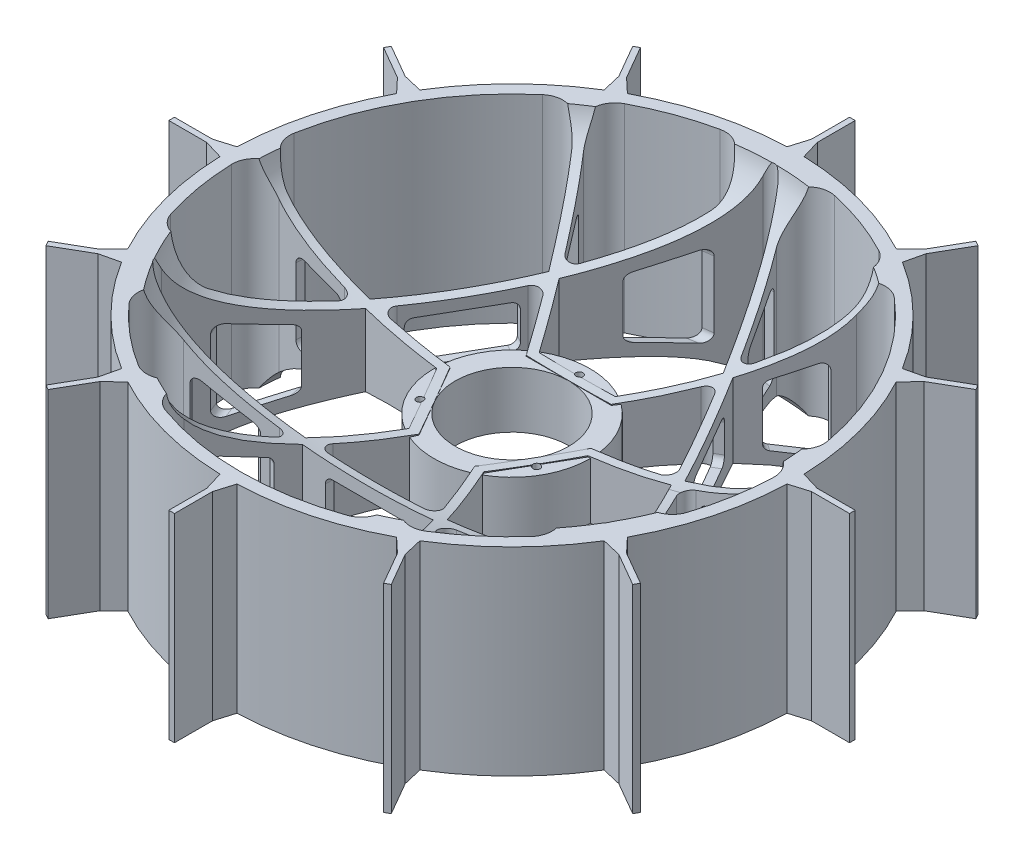
SolidWorks part; units mm, degrees
material "7075-O (SS)"
ref_plane "Front Plane" through (0, 0, 0) normal (0, 0, 1) x (1, 0, 0)
ref_plane "Top Plane" through (0, 0, 0) normal (0, 1, 0) x (1, 0, 0)
ref_plane "Right Plane" through (0, 0, 0) normal (1, 0, 0) x (0, 0, -1)
sketch "Sketch1" plane through (0, 0, 0) normal (0, 1, 0) x (1, 0, 0)
  circle A0 centre (0, 0) radius 100
  circle A1 centre (0, 0) radius 95.625
  dimension "D1" = 200
  dimension "D2" = 191.25
extrude "Boss-Extrude1" add sketch "Sketch1" along normal blind 70
sketch "Sketch5" plane through (0, 10, 0) normal (0, 1, 0) x (1, 0, 0)
  line L2 (-11.875, 8) -> (-11.875, -8)
  line L3 (11.875, -8) -> (11.875, 8)
  line L4 (-11.875, 8) -> (-11.875, -8)
  line L5 (11.875, -8) -> (11.875, 8)
  arc A15 (-4.1565, 8.4932) -> (-11.875, 8) centre (-8, 8) ccw
  arc A16 (-11.875, -8) -> (-8, -11.875) centre (-8, -8) ccw
  arc A17 (-8, -11.875) -> (-4.1565, -8.4932) centre (-8, -8) ccw
  arc A18 (-2.0488, -6.6387) -> (-4.1565, -8.4932) centre (-2.0488, -8.7637) ccw
  arc A19 (-1.5651, -6.6945) -> (-2.0488, -6.6387) centre (-2.0488, -8.7637) ccw
  arc A20 (-1.5651, -6.6945) -> (0, -6.875) centre (0, 0) ccw
  arc A21 (0, -6.875) -> (1.5651, -6.6945) centre (0, 0) ccw
  arc A22 (2.0488, -6.6387) -> (1.5651, -6.6945) centre (2.0488, -8.7637) ccw
  arc A23 (4.1565, -8.4932) -> (2.0488, -6.6387) centre (2.0488, -8.7637) ccw
  arc A24 (4.1565, -8.4932) -> (8, -11.875) centre (8, -8) ccw
  arc A25 (8, -11.875) -> (11.875, -8) centre (8, -8) ccw
  arc A26 (11.875, 8) -> (4.1565, 8.4932) centre (8, 8) ccw
  arc A27 (1.5651, 6.6945) -> (4.1565, 8.4932) centre (2.0488, 8.7637) ccw
  arc A28 (1.5651, 6.6945) -> (-1.5651, 6.6945) centre (0, 0) ccw
  arc A29 (-4.1565, 8.4932) -> (-1.5651, 6.6945) centre (-2.0488, 8.7637) ccw
  arc A30 (-4.1565, 8.4932) -> (-11.875, 8) centre (-8, 8) ccw
  arc A31 (-11.875, -8) -> (-8, -11.875) centre (-8, -8) ccw
  arc A32 (-8, -11.875) -> (-4.1565, -8.4932) centre (-8, -8) ccw
  arc A33 (-2.0488, -6.6387) -> (-4.1565, -8.4932) centre (-2.0488, -8.7637) ccw
  arc A34 (-1.5651, -6.6945) -> (-2.0488, -6.6387) centre (-2.0488, -8.7637) ccw
  arc A35 (-1.5651, -6.6945) -> (0, -6.875) centre (0, 0) ccw
  arc A36 (0, -6.875) -> (1.5651, -6.6945) centre (0, 0) ccw
  arc A37 (2.0488, -6.6387) -> (1.5651, -6.6945) centre (2.0488, -8.7637) ccw
  arc A38 (4.1565, -8.4932) -> (2.0488, -6.6387) centre (2.0488, -8.7637) ccw
  arc A39 (4.1565, -8.4932) -> (8, -11.875) centre (8, -8) ccw
  arc A40 (8, -11.875) -> (11.875, -8) centre (8, -8) ccw
  arc A41 (11.875, 8) -> (4.1565, 8.4932) centre (8, 8) ccw
  arc A42 (1.5651, 6.6945) -> (4.1565, 8.4932) centre (2.0488, 8.7637) ccw
  arc A43 (1.5651, 6.6945) -> (-1.5651, 6.6945) centre (0, 0) ccw
  arc A44 (-4.1565, 8.4932) -> (-1.5651, 6.6945) centre (-2.0488, 8.7637) ccw
  dimension "D1" = 0
extrude "Boss-Extrude5" add sketch "Sketch5" along normal blind 10 separate body
sketch "Sketch6" plane through (0, 20, 0) normal (0, 1, 0) x (1, 0, 0)
  circle A0 centre (0, 0) radius 17.5
  dimension "D1" = 35
extrude "Boss-Extrude6" add sketch "Sketch6" along normal blind 20
fillet "Fillet1" [suppressed] radius 5
fillet "Fillet2" [suppressed] radius 6
sketch "Sketch9" plane through (0, 10, 0) normal (0, -1, 0) x (1, 0, 0)
  circle A0 centre (0, 0) radius 1.5
extrude "Cut-Extrude3" cut sketch "Sketch9" against normal blind 5
ref_plane "Plane1" through (0, 22.5, 0) normal (0, 1, 0) x (1, 0, 0)
sketch "Sketch10" plane through (0, 22.5, 0) normal (0, 1, 0) x (1, 0, 0)
  line L0 (-55, 78.2249) -> (-15, 20)
  line L1 (-15, 20) -> (15, 20)
  line L2 (15, 20) -> (55, 78.2249)
  line L3 (0, 0) -> (0, 90.4108) construction
  line L4 (-52.5191, 79.9117) -> (-13.4212, 23)
  line L5 (-13.4212, 23) -> (13.4212, 23)
  line L6 (13.4212, 23) -> (52.5191, 79.9117)
  line L7 (-52.5273, 79.9237) -> (-13.4212, 23) construction
  line L8 (13.4212, 23) -> (52.5273, 79.9237) construction
  line L9 (9.8205, -22.9904) -> (40.2448, -86.7439)
  line L10 (13.208, -23.1231) -> (42.946, -85.4387)
  line L11 (26.6292, 0.1231) -> (13.208, -23.1231)
  line L12 (95.4651, 5.527) -> (26.6292, 0.1231)
  line L13 (95.2448, 8.5189) -> (24.8205, 2.9904)
  line L14 (24.8205, 2.9904) -> (9.8205, -22.9904)
  line L15 (-24.8205, 2.9904) -> (-95.2448, 8.5189)
  line L16 (-26.6292, 0.1231) -> (-95.4651, 5.527)
  line L17 (-13.208, -23.1231) -> (-26.6292, 0.1231)
  line L18 (-42.946, -85.4387) -> (-13.208, -23.1231)
  line L19 (-40.2448, -86.7439) -> (-9.8205, -22.9904)
  line L20 (-9.8205, -22.9904) -> (-24.8205, 2.9904)
  circle A0 centre (0, 0) radius 95.625 construction
  arc A1 (55, 78.2249) -> (52.5191, 79.9117) centre (0, 0) ccw
  arc A2 (-52.5191, 79.9117) -> (-55, 78.2249) centre (0, 0) ccw
  arc A3 (40.2448, -86.7439) -> (42.946, -85.4387) centre (0, 0) ccw
  arc A4 (95.4651, 5.527) -> (95.2448, 8.5189) centre (0, 0) ccw
  arc A5 (-95.2448, 8.5189) -> (-95.4651, 5.527) centre (0, 0) ccw
  arc A6 (-42.946, -85.4387) -> (-40.2448, -86.7439) centre (0, 0) ccw
  point P9 (0, 20)
  dimension "D1" = 30
  dimension "D2" = 40
  dimension "D4" = 20
  dimension "D3" = 3
  dimension "D5" = 3
extrude "Boss-Extrude7" add sketch "Sketch10" along normal up to surface and the other way up to surface up to face at (0, 70, 100) other way up to face at (0, 0, 100)
sketch "Sketch12" plane through (0, 22.5, 0) normal (0, 1, 0) x (1, 0, 0)
  line L1 (-82.8137, -47.8125) -> (-86.2778, -47.8125)
  line L12 (0, 101.625) -> (0, 95.625)
  line L154 (-19.9186, -11.5) -> (-82.8137, -47.8125) construction
  line L159 (-26.6292, 0.1231) -> (-13.208, -23.1231) construction
  line L199 (0, 23) -> (0, 95.625) construction
  line L202 (13.4212, 23) -> (-13.4212, 23) construction
  line L227 (0, 95.625) -> (-82.8137, -47.8125)
  line L228 (0, 101.625) -> (-86.2778, -47.8125)
  line L241 (0, 0) -> (0, 17.5) construction
  arc A1 (52.5191, 79.9117) -> (-52.5191, 79.9117) centre (0, 0) ccw construction
  arc A4 (-95.4651, 5.527) -> (-42.946, -85.4387) centre (0, 0) ccw construction
  circle A6 centre (0, 0) radius 17.5 construction
  dimension "D4" = 3
extrude "Boss-Extrude9" add sketch "Sketch12" along normal up to surface (47.5 mm away) and the other way up to surface (22.5 mm away) up to face at (0, 70, -55.3842) other way up to face at (0, 0, 0)
sketch "Sketch16" plane through (0, 0, 0) normal (0, 0, 1) x (1, 0, 0)
  line L0 (0, 0) -> (0, 92.688) construction
  line L1 (92.5, 70) -> (17.5, 70)
  line L2 (42.946, 0) -> (95.625, 0) construction
  line L4 (0, 20) -> (17.5, 20) construction
  line L7 (0, 40) -> (17.5, 40) construction
  line L10 (92.5, 0) -> (17.5, 0)
  line L11 (100, 70) -> (-100, 70) construction
  line L14 (95.625, 70) -> (42.946, 70) construction
  line L15 (-100, 0) -> (100, 0) construction
  line L17 (17.5, 20) -> (17.5, 0)
  line L18 (17.5, 40) -> (17.5, 70)
  line L19 (100, 70) -> (-100, 70) construction
  spline S0 degree 3 poles (17.5, 40) (32.4984, 40.5235) (58.0939, 42.4991) (89.7048, 56.2163) (92.5, 70) knots 0 0 0 0 0.512398 1 1 1 1
  spline S1 degree 3 poles (92.5, 0) (86.6455, 10.3794) (60.1621, 19.8586) (33.4171, 20.5239) (17.5, 20) knots 0 0 0 0 0.409755 1 1 1 1
  dimension "D5" = 80.9367
  dimension "D6" = 85.7724
  dimension "D1" = 30
  dimension "D2" = 20
  dimension "D3" = 17.5
  dimension "D4" = 17.5
pattern_circular "CirPattern3" count 3 over 360 about axis through (0, 70, 0) along (0, -1, 0) of "Boss-Extrude9" reverse direction yes
fillet "Fillet3" radius 8 18 edges at (-95.2448, 35, -8.5189) (40.2448, 35, 86.7439) (-40.2448, 35, 86.7439) (95.2448, 35, -8.5189) (55, 35, -78.2249) (-55, 35, -78.2249) (-95.4651, 35, -5.527) (-84.5087, 35, 44.7484) (-81.0076, 35, 50.8125) (81.0076, 35, 50.8125) (-42.946, 35, 85.4387) (42.946, 35, 85.4387) (84.5087, 35, 44.7484) (3.5011, 35, -95.5609) (95.4651, 35, -5.527) (-3.5011, 35, -95.5609) (52.5191, 35, -79.9117) (-52.5191, 35, -79.9117)
fillet "Fillet4" radius 3 15 edges at (30.5738, 35, -42.6696) (52.2399, 35, -5.1429) (21.6661, 35, 47.8125) (-21.6661, 35, 47.8125) (-52.2399, 35, -5.1429) (-30.5738, 35, -42.6696) (-57.2158, 35, -2.5243) (-26.4218, 35, 50.8125) (26.4218, 35, 50.8125) (57.2158, 35, -2.5243) (30.794, 35, -48.2882) (-30.794, 35, -48.2882) (82.8137, 35, 47.8125) (-82.8137, 35, 47.8125) (0, 35, -95.625)
sketch "Sketch17" plane through (0, 70, 0) normal (0, 1, 0) x (1, 0, 0)
  line L0 (0, 0) -> (0, 135.3028) construction
  line L5 (-3, 99.955) -> (0, 109.955)
  line L6 (0, 109.955) -> (3, 99.955)
  line L7 (-3, 99.955) -> (3, 99.955)
  circle A2 centre (0, 0) radius 100 construction
  point P9 (0, 99.955)
  dimension "D1" = 10
  dimension "D2" = 3
sketch "Sketch4" plane through (0, 70, 0) normal (0, 1, 0) x (1, 0, 0)
  line L0 (0, 0) -> (0, 100.0041) construction
  line L1 (1, 99.9041) -> (-1, 99.9041)
  line L2 (-1, 99.9041) -> (-1, 120.0041)
  line L3 (-1, 120.0041) -> (1, 120.0041)
  line L4 (1, 120.0041) -> (1, 99.9041)
  point P9 (0, 99.9041)
  dimension "D1" = 2
  dimension "D2" = 0.1
  dimension "D3" = 20.1
extrude "Boss-Extrude10" add sketch "Sketch17" against normal up to surface (70 mm away) up to face at (78.9295, 0, 9.9484)
extrude "Boss-Extrude11" add sketch "Sketch4" against normal up to surface (70 mm away) up to face at (0.079, 0, -0.6766)
pattern_circular "CirPattern2" count 12 over 360 about axis through (0, 70, 0) along (0, 1, 0) of "Boss-Extrude11", "Boss-Extrude10"
revolve "Cut-Revolve1" cut sketch "Sketch16" angle 360 about L0
ref_plane "Plane2" through (0, 30, 0) normal (0, -1, 0) x (-1, 0, 0)
sketch "Sketch18" plane through (0, 30, 0) normal (0, -1, 0) x (-1, 0, 0)
  circle A0 centre (0, 0) radius 75
  dimension "D1" = 150
sketch "Sketch20" plane through (0.8561, 0, 0.5882) normal (0.8242, 0, 0.5662) x (0.5662, 0, -0.8242)
  line L0 (80.6576, 43.5678) -> (80.6576, 20.0839)
  line L1 (77.5105, 17.6691) -> (65.1592, 20.9787)
  line L2 (63.3062, 23.3935) -> (63.3062, 40.2583)
  line L3 (65.1592, 42.6731) -> (77.5105, 45.9826)
  line L4 (55.8062, 31.4022) -> (87.1576, 33.1732) construction
  line L5 (55.8062, 18.3431) -> (55.8062, 44.4613) construction
  line L6 (87.1576, 6.7241) -> (87.1576, 59.6223) construction
  arc A0 (80.6576, 20.0839) -> (77.5105, 17.6691) centre (78.1576, 20.0839) cw
  arc A1 (65.1592, 20.9787) -> (63.3062, 23.3935) centre (65.8062, 23.3935) cw
  arc A2 (63.3062, 40.2583) -> (65.1592, 42.6731) centre (65.8062, 40.2583) cw
  arc A3 (80.6576, 43.5678) -> (77.5105, 45.9826) centre (78.1576, 43.5678) ccw
  point P10 (63.3062, 31.8259)
  point P13 (80.6576, 16.8259)
  point P20 (80.6576, 46.8259)
  dimension "D6" = 2.5
  dimension "D1" = 30
  dimension "D2" = 75
  dimension "D3" = 75
  dimension "D4" = 6.5
  dimension "D5" = 7.5
sweep "Cut-Sweep1" cut profiles "Sketch20" path "Sketch18"
sketch "Sketch22" plane through (0, 10, 0) normal (0, -1, 0) x (1, 0, 0)
  circle A0 centre (0, 0) radius 27.5
  circle A1 centre (0, 0) radius 17.5
  dimension "D1" = 55
  dimension "D2" = 35
extrude "Boss-Extrude12" add sketch "Sketch22" against normal up to surface (30 mm away) up to face at (0, 40, 17.5)
sketch "Sketch24" plane through (0, 10, 0) normal (0, -1, 0) x (1, 0, 0)
  circle A0 centre (0, 0) radius 20
  dimension "D1" = 40
extrude "Cut-Extrude5" cut sketch "Sketch24" against normal through all
sketch "Sketch25" plane through (0, 10, 0) normal (0, -1, 0) x (-1, 0, 0)
  line L0 (0, 0) -> (0, 23.75) construction
  circle A4 centre (0, 23.75) radius 1.25
  dimension "D1" = 23.75
  dimension "D2" = 2.5
extrude "Cut-Extrude6" cut sketch "Sketch25" against normal through all
pattern_circular "CirPattern4" count 3 over 360 about axis through (0, 117.7817, 0) along (0, -1, 0) of "Cut-Extrude6"
sketch "Sketch26" plane through (44.0049, 0, -25.4063) normal (0.866, 0, -0.5) x (-0.5, 0, -0.866)
  line L1 (-23.0977, 31.4022) -> (23.0977, 31.4022) construction
  line L2 (-23.0977, 44.4613) -> (-23.0977, 18.3431) construction
  line L3 (23.0977, 18.3431) -> (23.0977, 44.4613) construction
  line L5 (-12.5, 23.9022) -> (12.5, 23.9022)
  line L6 (-15, 26.4022) -> (-15, 36.4022)
  line L7 (-12.5, 38.9022) -> (12.5, 38.9022)
  line L8 (15, 26.4022) -> (15, 36.4022)
  line L9 (-15, 23.9022) -> (15, 38.9022) construction
  line L10 (-15, 38.9022) -> (15, 23.9022) construction
  arc A0 (12.5, 38.9022) -> (15, 36.4022) centre (12.5, 36.4022) cw
  arc A1 (12.5, 23.9022) -> (15, 26.4022) centre (12.5, 26.4022) ccw
  arc A2 (-12.5, 23.9022) -> (-15, 26.4022) centre (-12.5, 26.4022) cw
  arc A3 (-15, 36.4022) -> (-12.5, 38.9022) centre (-12.5, 36.4022) cw
  point P0 (0, 31.43)
  point P13 (0, 31.4022)
  point P18 (0, 31.53)
  point P19 (0, 31.43)
  dimension "D3" = 2.5
  dimension "D1" = 30
  dimension "D2" = 15
extrude "Cut-Extrude7" cut sketch "Sketch26" against normal up to next
pattern_circular "CirPattern5" count 3 over 360 about axis through (0, 40, 0) along (0, 1, 0) of "Cut-Extrude7"
sketch "Sketch27" plane through (0, 10, 0) normal (0, -1, 0) x (1, 0, 0)
  circle A0 centre (0, 0) radius 27.5
extrude "Cut-Extrude8" cut sketch "Sketch27" against normal blind 10.2
